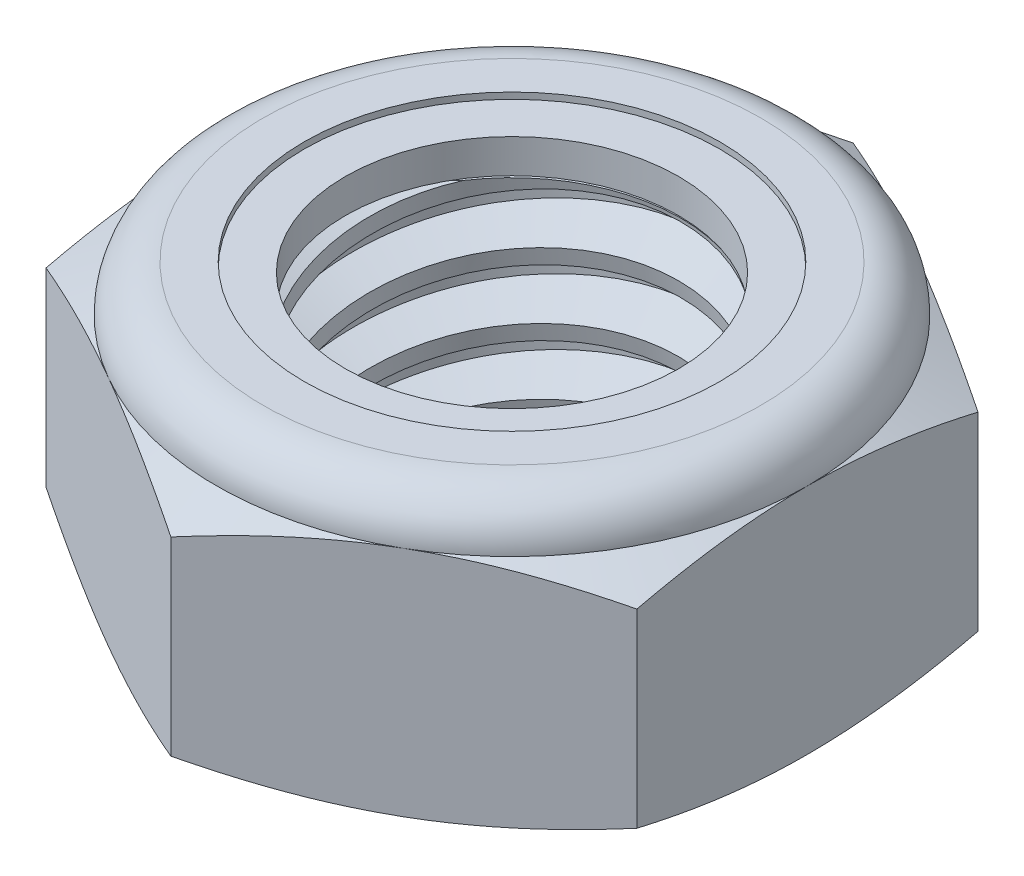
SolidWorks part; units mm, degrees
ref_plane "Front" through (0, 0, 0) normal (0, 0, 1) x (1, 0, 0)
ref_plane "Top" through (0, 0, 0) normal (0, 1, 0) x (1, 0, 0)
ref_plane "Right" through (0, 0, 0) normal (1, 0, 0) x (0, 0, -1)
sketch "Sketch1" plane through (0, 0, 0) normal (0, 1, 0) x (1, 0, 0)
  line L1 (0, 8.2489) -> (-7.1438, 4.1244)
  line L2 (-7.1438, 4.1244) -> (-7.1438, -4.1244)
  line L3 (-7.1438, -4.1244) -> (0, -8.2489)
  line L4 (0, -8.2489) -> (7.1438, -4.1244)
  line L5 (7.1438, -4.1244) -> (7.1437, 4.1244)
  line L6 (7.1437, 4.1244) -> (0, 8.2489)
  circle A0 centre (0, 0) radius 7.1438 construction
  dimension "Hex Flats" = 14.2875
extrude "Extrude1" add sketch "Sketch1" along normal blind 6.7469
sketch "Sketch2" plane through (0, 0, 0) normal (1, 0, 0) x (0, 0, -1)
  line L0 (-4.7625, 0) -> (-4.7625, 6.7469) construction
  line L1 (0, 0) -> (4.7625, 0)
  line L2 (0, 0) -> (0, 6.7469)
  line L3 (0, 6.7469) -> (4.7625, 6.7469)
  line L4 (4.7625, 0) -> (4.7625, 6.7469)
  line L5 (-4.1244, 6.7469) -> (4.1244, 6.7469) construction
  line L7 (0, -4.7625) -> (0, 0) construction
  dimension "Thread Dia" = 9.525
revolve "Revolve1" add sketch "Sketch2" angle 360 about L7
sketch "Sketch3" plane through (0, 0, 0) normal (1, 0, 0) x (0, 0, -1)
  line L0 (4.7625, 6.7469) -> (-4.7625, 6.7469) construction
  line L1 (-4.7625, 6.7469) -> (-4.7625, 5.1594) construction
  line L2 (-4.7625, 5.1594) -> (4.7625, 6.7469) construction
  line L3 (4.7625, 6.7469) -> (4.7951, 6.5511) construction
  line L4 (4.7951, 6.5511) -> (5.0235, 5.181)
  line L5 (5.0235, 5.181) -> (4.0944, 5.5291)
  line L6 (4.0944, 5.5291) -> (4.0291, 5.9205)
  line L7 (4.0291, 5.9205) -> (4.7951, 6.5511)
  line L8 (4.0617, 5.7248) -> (4.9093, 5.8661) construction
  line L9 (4.7625, 6.7469) -> (4.7625, 5.8416) construction
  line L10 (4.7625, 5.8416) -> (-4.7625, 4.2541) construction
  line L11 (-4.7625, 4.2541) -> (-4.7625, 5.1594) construction
  line L12 (-0.2832, 6.7469) -> (0.2832, 3.3488) construction
  line L13 (-4.7625, 0) -> (-4.7625, 6.7469) construction
  line L14 (0, 6.7469) -> (4.7625, 6.7469) construction
  line L15 (4.7625, 0) -> (4.7625, 6.7469) construction
  point P13 (0, 5.0478)
  dimension "D1" = 0.1984
  dimension "D2" = 0.3969
  dimension "Thread Pitch" = 1.5875
  dimension "D4" = 60
  dimension "D5" = 1.5875
revolve "Cut-Revolve1" cut sketch "Sketch3" angle 360 about L12
pattern_linear "LPattern1" count 4 spacing 1.5875 along (0, -1, 0) count 2 spacing 1.5875 along (0, 1, 0) of "Cut-Revolve1"
sketch "Sketch4" plane through (0, 0, 0) normal (1, 0, 0) x (0, 0, -1)
  line L0 (0, 6.7469) -> (4.7625, 6.7469)
  line L1 (4.7625, 6.7469) -> (4.0291, 6.4049)
  line L2 (4.0291, 6.4049) -> (4.0291, 0.342)
  line L3 (4.0291, 0.342) -> (4.7625, 0)
  line L4 (4.7625, 0) -> (0, 0)
  line L5 (0, 0) -> (0, 6.7469)
  line L6 (4.7625, 0) -> (4.7625, 6.7469) construction
  line L7 (0, 6.7469) -> (4.7625, 6.7469) construction
  line L8 (0, 0) -> (4.7625, 0) construction
  line L9 (0, 0) -> (0, 6.7469) construction
  line L10 (0, 6.7469) -> (0, 7.5561) construction
  dimension "D1" = 25
revolve "Cut-Revolve2" cut sketch "Sketch4" angle 360 about L10
combine bodies "Combine1" operation type subtract main body 112 bodies to subtract 111
sketch "Sketch5" plane through (0, 0, 0) normal (1, 0, 0) x (0, 0, -1)
  line L0 (0, 0) -> (7.1438, 0)
  line L1 (7.1438, 0) -> (8.2489, 0.5153)
  line L2 (8.2489, 0.5153) -> (8.2489, 5.1071)
  line L3 (8.2489, 5.1071) -> (7.1438, 5.6224)
  line L4 (6.0193, 6.7469) -> (6.0193, 8.0169)
  line L5 (6.0193, 8.0169) -> (9.5189, 8.0169)
  line L6 (9.5189, 8.0169) -> (9.5189, -1.27)
  line L7 (9.5189, -1.27) -> (0, -1.27)
  line L8 (0, -1.27) -> (0, 0)
  line L9 (7.1438, 5.6224) -> (7.1438, 0) construction
  line L10 (0, 0) -> (4.7625, 0) construction
  line L13 (8.2489, 2.8112) -> (9.5189, 2.8112) construction
  line L14 (8.2489, 6.7469) -> (8.2489, 0) construction
  line L15 (0, 0) -> (0, 8.0169) construction
  line L20 (0, 8.0169) -> (6.0193, 8.0169) construction
  line L22 (0, 6.7469) -> (4.7625, 6.7469) construction
  arc A0 (7.1438, 5.6224) -> (6.0193, 6.7469) centre (6.0193, 5.6224) ccw
  dimension "D1" = 25
  dimension "D2" = 1.27
  dimension "D3" = 6.7469
  dimension "D4" = 1.1245
revolve "Cut-Revolve3" cut sketch "Sketch5" angle 360 about L15
sketch "Sketch6" plane through (0, 0, 0) normal (1, 0, 0) x (0, 0, -1)
  line L0 (0, 5.6224) -> (6.9914, 5.6224)
  line L1 (6.0193, 6.5945) -> (5.0242, 6.5945)
  line L2 (0, 8.0169) -> (0, 5.6224)
  line L3 (5.0242, 8.0169) -> (0, 8.0169)
  line L4 (0, 8.0169) -> (6.0193, 8.0169) construction
  line L5 (0, 0) -> (0, 8.0169) construction
  line L6 (0, 8.0169) -> (0, 44.323) construction
  line L7 (5.0242, 6.5945) -> (5.0242, 8.0169)
  line L8 (6.0193, 6.7469) -> (6.0193, 6.5945) construction
  line L9 (5.0242, 6.5945) -> (4.0291, 6.5945) construction
  line L10 (4.0291, 6.5945) -> (4.0291, 6.4049) construction
  arc A0 (6.9914, 5.6224) -> (6.0193, 6.5945) centre (6.0193, 5.6224) ccw
  arc A1 (7.1438, 5.6224) -> (6.0193, 6.7469) centre (6.0193, 5.6224) ccw construction
  dimension "D1" = 0.1524
revolve "Cut-Revolve4" cut sketch "Sketch6" angle 360 about L6
sketch "Sketch7" plane through (0, 0, 0) normal (1, 0, 0) x (0, 0, -1)
  line L0 (4.0291, 5.6986) -> (6.9119, 5.6986)
  line L1 (6.0193, 6.5183) -> (4.0291, 6.5183)
  line L2 (4.0291, 6.5183) -> (4.0291, 5.6986)
  line L3 (4.0291, 5.6986) -> (0, 5.6986) construction
  line L4 (0, 5.6986) -> (0, 6.5183) construction
  line L5 (0, 6.5183) -> (4.0291, 6.5183) construction
  line L6 (4.0291, 5.6986) -> (4.0291, 5.6224) construction
  line L7 (0, 5.6224) -> (6.9914, 5.6224) construction
  line L8 (6.0193, 6.5183) -> (6.0193, 6.5945) construction
  arc A0 (6.9119, 5.6986) -> (6.0193, 6.5183) centre (6.0193, 5.6224) ccw
  arc A2 (6.9914, 5.6224) -> (6.0193, 6.5945) centre (6.0193, 5.6224) ccw construction
  dimension "D1" = 0.0762
revolve "Revolve2" add sketch "Sketch7" angle 360 about L4
equation "\"D1@Sketch3\"=\"Thread Pitch@Sketch3\"/8"
equation "\"D2@Sketch3\"=\"Thread Pitch@Sketch3\"/4"
equation "\"D5@Sketch3\"=\"Thread Pitch@Sketch3\""
equation "\"D4@LPattern1\"=\"Thread Pitch@Sketch3\""
equation "\"D3@LPattern1\"=\"Thread Pitch@Sketch3\""
equation "\"D1@LPattern1\"=\"Height@Extrude1\"/\"Thread Pitch@Sketch3\""
equation "\"D4@Sketch5\"=\"Height@Extrude1\"/6"
